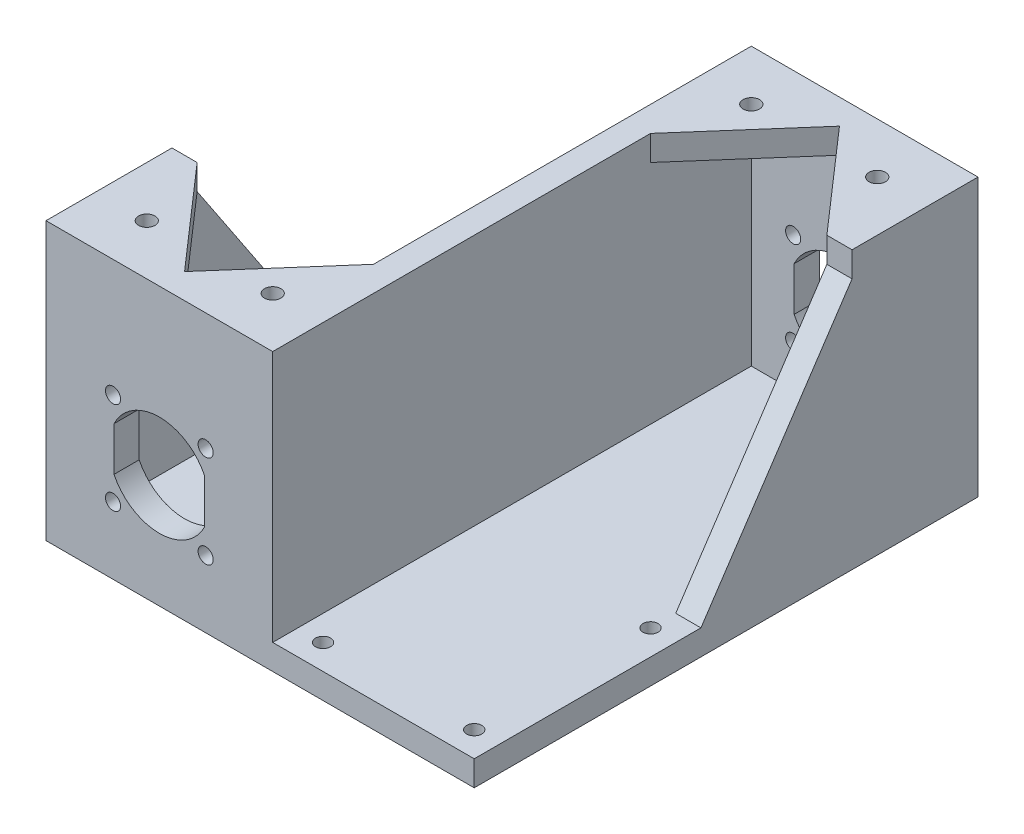
SolidWorks part; units mm, degrees
ref_plane "Plan de face" through (0, 0, 0) normal (0, 0, 1) x (1, 0, 0)
ref_plane "Plan de dessus" through (0, 0, 0) normal (0, 1, 0) x (1, 0, 0)
ref_plane "Plan de droite" through (0, 0, 0) normal (1, 0, 0) x (0, 0, -1)
sketch "Esquisse1" plane through (0, 0, 0) normal (0, 0, 1) x (1, 0, 0)
  line L0 (45, 0) -> (0, 45) construction
  line L1 (0, 0) -> (45, 0)
  line L2 (0, 0) -> (0, 45)
  line L3 (0, 45) -> (0, 55)
  line L4 (45, 0) -> (45, 45)
  line L5 (0, 0) -> (45, 45) construction
  line L6 (22.5, 45) -> (22.5, 0) construction
  line L7 (13.5, 26.8589) -> (13.5, 18.1411)
  line L8 (45, 22.5) -> (0, 22.5) construction
  line L9 (31.5, 26.8589) -> (31.5, 18.1411)
  line L10 (0, 55) -> (45, 55)
  line L11 (45, 55) -> (45, 45)
  line L12 (0, 45) -> (45, 45) construction
  arc A0 (13.5, 18.1411) -> (31.5, 18.1411) centre (22.5, 22.5) ccw
  circle A1 centre (31.6924, 31.6924) radius 1.5
  circle A2 centre (31.6924, 13.3076) radius 1.5
  circle A3 centre (13.3076, 13.3076) radius 1.5
  circle A4 centre (13.3076, 31.6924) radius 1.5
  arc A5 (31.5, 26.8589) -> (13.5, 26.8589) centre (22.5, 22.5) ccw
  dimension "D3" = 20
  dimension "D5" = 3
  dimension "D1" = 45
  dimension "D2" = 45
  dimension "D4" = 13
  dimension "D6" = 9
  dimension "D7" = 55
extrude "Extrusion1" add sketch "Esquisse1" along normal blind 5
sketch "Esquisse2" plane through (0, 0, 5) normal (0, 0, 1) x (1, 0, 0)
  line L0 (45, 0) -> (45, 55) construction
  line L1 (0, 0) -> (45, 0)
  line L2 (0, 0) -> (0, 5)
  line L3 (0, 5) -> (45, 5)
  line L4 (45, 0) -> (45, 5)
  dimension "D1" = 5
extrude "Extrusion2" add sketch "Esquisse2" along normal blind 95
sketch "Esquisse3" plane through (45, 0, 0) normal (1, 0, 0) x (0, 0, -1)
  line L0 (-5, 5) -> (-5, 55)
  line L1 (-25, 50) -> (-55, 5)
  line L2 (-100, 5) -> (-5, 5) construction
  line L3 (-55, 5) -> (-5, 5)
  line L4 (-25, 55) -> (-5, 55)
  line L7 (-25, 50) -> (-25, 55)
  dimension "D1" = 50
  dimension "D2" = 20
  dimension "D3" = 5
extrude "Extrusion3" add sketch "Esquisse3" against normal blind 5
sketch "Esquisse4" plane through (0, 0, 0) normal (-1, 0, 0) x (0, 0, 1)
  line L0 (5, 5) -> (5, 55)
  line L1 (5, 55) -> (100, 55)
  line L2 (100, 55) -> (100, 5)
  line L3 (100, 5) -> (5, 5)
  line L4 (5, 55) -> (0, 55) construction
  line L5 (5, 55) -> (5, 5) construction
extrude "Extrusion4" add sketch "Esquisse4" against normal blind 5
sketch "Esquisse5" plane through (0, 0, 0) normal (-1, 0, 0) x (0, 0, 1)
  line L0 (100, 55) -> (100, 0) construction
  line L1 (0, 0) -> (100, 0)
  line L2 (0, 0) -> (0, 5)
  line L3 (0, 5) -> (100, 5)
  line L4 (100, 0) -> (100, 5)
  dimension "D1" = 5
extrude "Extrusion5" add sketch "Esquisse5" along normal blind 40
sketch "Esquisse6" plane through (0, 0, 100) normal (0, 0, 1) x (1, 0, 0)
  line L0 (0, 5) -> (0, 55)
  line L1 (0, 55) -> (-40, 55)
  line L2 (-40, 55) -> (-40, 5)
  line L3 (-40, 5) -> (0, 5)
  line L4 (0, 55) -> (0, 5) construction
  dimension "D1" = 50
extrude "Extrusion6" add sketch "Esquisse6" against normal blind 5
sketch "Esquisse7" plane through (-40, 0, 0) normal (-1, 0, 0) x (0, 0, 1)
  line L0 (95, 5) -> (95, 55)
  line L1 (95, 55) -> (100, 55) construction
  line L2 (95, 5) -> (0, 5) construction
  line L3 (45, 5) -> (95, 5)
  line L6 (95, 55) -> (75, 55)
  line L7 (75, 55) -> (75, 50)
  line L8 (75, 50) -> (45, 5)
  dimension "D1" = 50
  dimension "D2" = 20
  dimension "D3" = 5
extrude "Extrusion7" add sketch "Esquisse7" against normal blind 5
sketch "Esquisse8" plane through (0, 0, 100) normal (0, 0, 1) x (1, 0, 0)
  line L0 (5, 5) -> (5, 0) construction
  line L1 (-40, 0) -> (45, 0) construction
  line L2 (-40, 45) -> (-40, 0) construction
  line L4 (-40, 45) -> (5, 45) construction
  line L5 (-26.5, 18.1411) -> (-26.5, 26.8589)
  line L8 (-40, 0) -> (5, 45) construction
  line L9 (-8.5, 18.1411) -> (-8.5, 26.8589)
  line L10 (5, 55) -> (-40, 55) construction
  line L11 (-17.5, 55) -> (-17.5, 0) construction
  line L13 (-40, 45) -> (5, 0) construction
  line L14 (5, 5) -> (5, 55) construction
  arc A0 (-26.5, 18.1411) -> (-8.5, 18.1411) centre (-17.5, 22.5) ccw
  circle A1 centre (-8.3076, 13.3076) radius 1.5
  circle A2 centre (-8.3076, 31.6924) radius 1.5
  circle A3 centre (-26.6924, 31.6924) radius 1.5
  circle A4 centre (-26.6924, 13.3076) radius 1.5
  arc A5 (-8.5, 26.8589) -> (-26.5, 26.8589) centre (-17.5, 22.5) ccw
  dimension "D1" = 20
  dimension "D2" = 3
  dimension "D6" = 3
  dimension "D3" = 13
  dimension "D4" = 9
  dimension "D5" = 45
  dimension "D7" = 13
extrude "Enlèv. mat.-Extru.1" cut sketch "Esquisse8" against normal up to next
sketch "Esquisse9" plane through (0, 5, 0) normal (0, 1, 0) x (-1, 0, 0)
  line L0 (-45, 100) -> (-5, 100) construction
  line L1 (-45, 100) -> (-45, 55) construction
  line L2 (40, 0) -> (0, 0) construction
  line L3 (40, 45) -> (40, 0) construction
  circle A0 centre (-40, 95) radius 1.5
  circle A1 centre (-10, 95) radius 1.5
  circle A2 centre (35, 5) radius 1.5
  circle A3 centre (5, 5) radius 1.5
  circle A4 centre (-40, 60) radius 1.5
  circle A5 centre (35, 40) radius 1.5
  dimension "D1" = 3
  dimension "D2" = 3
  dimension "D4" = 5
  dimension "D6" = 35
  dimension "D7" = 5
  dimension "D9" = 3
  dimension "D10" = 3
  dimension "D13" = 3
  dimension "D16" = 3
  dimension "D17" = 40
  dimension "D18" = 5
  dimension "D3" = 5
  dimension "D5" = 5
  dimension "D8" = 5
  dimension "D11" = 35
  dimension "D12" = 5
  dimension "D14" = 5
  dimension "D15" = 40
extrude "Enlèv. mat.-Extru.2" cut sketch "Esquisse9" against normal up to next
sketch "Esquisse11" plane through (0, 55, 0) normal (0, 1, 0) x (1, 0, 0)
  line L0 (22.5, -5) -> (5, -25)
  line L2 (5, -100) -> (5, -5) construction
  line L3 (45, 0) -> (0, 0) construction
  line L4 (5, -25) -> (5, 0)
  line L5 (40, -5) -> (5, -5) construction
  line L6 (5, 0) -> (40, 0)
  line L7 (40, 0) -> (40, -25)
  line L8 (40, -25) -> (22.5, -5)
  dimension "D1" = 25
extrude "Boss.-Extru.1" add sketch "Esquisse11" against normal blind 5
sketch "Esquisse12" plane through (0, 55, 0) normal (0, 1, 0) x (1, 0, 0)
  line L0 (0, -75) -> (-17.5, -95)
  line L1 (0, -95) -> (0, 0) construction
  line L2 (0, -95) -> (-35, -95) construction
  line L3 (0, -75) -> (0, -100)
  line L4 (5, -100) -> (-40, -100) construction
  line L5 (0, -95) -> (-35, -95) construction
  line L6 (0, -100) -> (-35, -100)
  line L7 (-35, -100) -> (-35, -75)
  line L8 (-35, -75) -> (-17.5, -95)
  dimension "D1" = 25
extrude "Boss.-Extru.2" add sketch "Esquisse12" against normal blind 5
hole_wizard "Dégagement #41" positions "Esquisse14" profile "Esquisse15" hole size "#4" standard "Ansi Pouces"
sketch "Esquisse14" plane through (0, 55, 0) normal (0, 1, 0) x (-1, 0, 0)
  line L0 (-45, 0) -> (0, 0) construction
  line L1 (-45, 25) -> (-45, 0) construction
  line L2 (0, 75) -> (0, 0) construction
  line L3 (-5, 100) -> (-5, 25) construction
  line L4 (-5, 100) -> (40, 100) construction
  line L5 (40, 75) -> (40, 100) construction
  point P0 (-10, 10)
  point P1 (-35, 10)
  point P3 (30, 90)
  point P5 (5, 90)
  dimension "D1" = 10
  dimension "D2" = 10
  dimension "D3" = 10
  dimension "D4" = 10
  dimension "D5" = 10
  dimension "D6" = 10
  dimension "D7" = 10
  dimension "D8" = 10
sketch "Esquisse15" plane through (10, 55, 10) normal (1, 0, 0) x (0, 0, 1)
  line L0 (0, 0) -> (0, 10.9806)
  line L1 (0, 10.9806) -> (1.6319, 10)
  line L2 (1.6319, 10) -> (1.6319, 0)
  line L5 (1.6319, 0) -> (0, 0)
  line L10 (0, 10.9806) -> (-1.632, 10) construction
  line L11 (0, -6.35) -> (0, 107.95) construction
  dimension "Diamètre du perçage" = 3.2639
  dimension "Profondeur du perçage" = 10
  dimension "Angle de pointe" = 118
